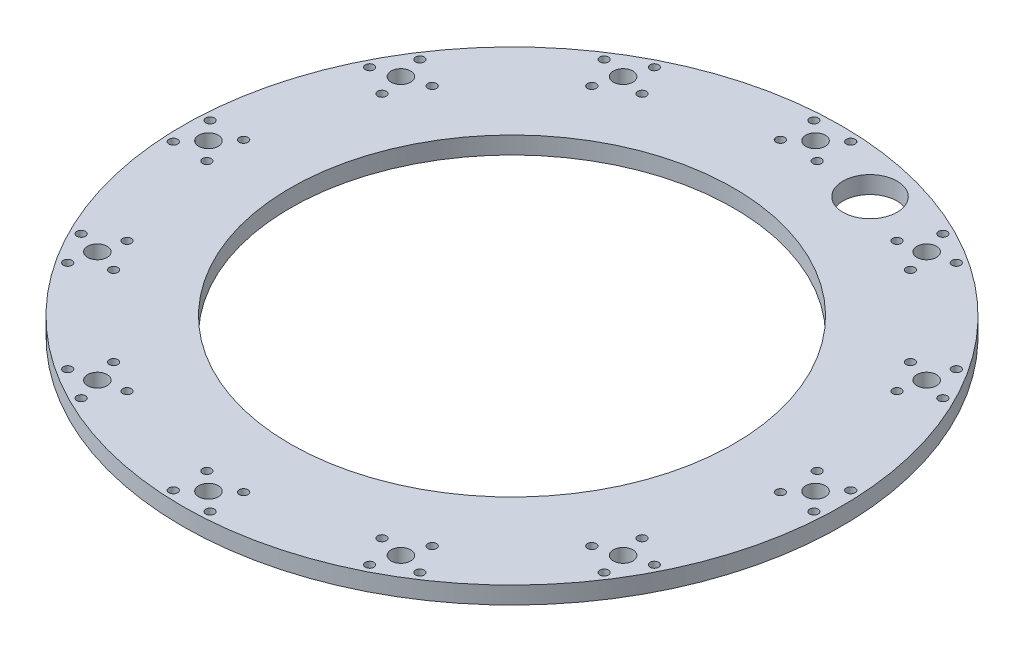
SolidWorks part; units mm, degrees
material "Balsa"
ref_plane "Ebene vorne" through (0, 0, 0) normal (0, 0, 1) x (1, 0, 0)
ref_plane "Ebene oben" through (0, 0, 0) normal (0, 1, 0) x (1, 0, 0)
ref_plane "Ebene rechts" through (0, 0, 0) normal (1, 0, 0) x (0, 0, -1)
sketch "Sketch1" plane through (0, 0, 0) normal (0, 1, 0) x (1, 0, 0)
  circle A0 centre (0, 0) radius 51.2
  circle A1 centre (0, 0) radius 76.1
  dimension "D1" = 152.2
  dimension "D2" = 102.4
extrude "Boss-Extrude1" add sketch "Sketch1" along normal blind 4
sketch "Sketch2" plane through (0, 4, 0) normal (0, 1, 0) x (1, 0, 0)
  line L0 (0, 78.5044) -> (0, 60.1888) construction
  line L1 (7.9546, 70.0914) -> (-11.9341, 70.0914) construction
  circle A0 centre (0, 70.0914) radius 2.25
  circle A1 centre (4.2466, 73.9682) radius 1
  circle A2 centre (4.2466, 66.2147) radius 1
  circle A3 centre (-4.2466, 66.2147) radius 1
  circle A4 centre (-4.2466, 73.9682) radius 1
  dimension "D1" = 4.5
  dimension "D3" = 2
  dimension "D2" = 11.5
extrude "Cut-Extrude1" cut sketch "Sketch2" against normal through all
ref_axis "Axis1" through (0, -0.2, 0) along (0, 1, 0)
pattern_circular "CirPattern1" count 12 over 360 about axis through (0, -0.2, 0) along (0, 1, 0) of "Cut-Extrude1"
sketch "Sketch3" plane through (0, 4, 0) normal (0, 1, 0) x (1, 0, 0)
  line L0 (17.4703, 65.2) -> (0, 0) construction
  line L1 (0, 0) -> (0, 80.521) construction
  circle A0 centre (17.4703, 65.2) radius 6.25
  dimension "D1" = 12.5
  dimension "D3" = 15
  dimension "D2" = 67.5
extrude "Cut-Extrude2" cut sketch "Sketch3" against normal blind 10
